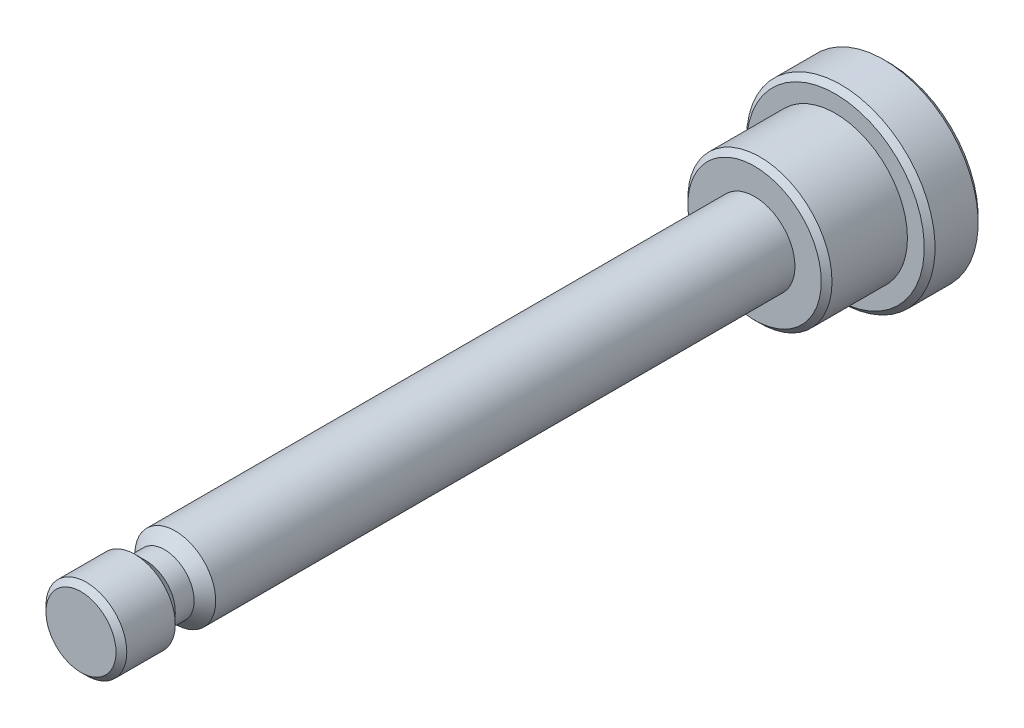
SolidWorks part; units mm, degrees
ref_plane "Front" through (0, 0, 0) normal (0, 0, 1) x (1, 0, 0)
ref_plane "Top" through (0, 0, 0) normal (0, 1, 0) x (1, 0, 0)
ref_plane "Right" through (0, 0, 0) normal (1, 0, 0) x (0, 0, -1)
sketch "Sketch1" plane through (0, 0, 0) normal (0, 0, 1) x (1, 0, 0)
  circle A0 centre (0, 0) radius 2.675
  dimension "D1" = 5.35
extrude "Countersink" add sketch "Sketch1" against normal blind 3
sketch "Sketch2" plane through (0, 0, 0) normal (0, 0, 1) x (1, 0, 0)
  circle A0 centre (0, 0) radius 1.5
  dimension "D1" = 3
extrude "Shaft" add sketch "Sketch2" along normal blind 25
sketch "Sketch3" plane through (0, 0, -3) normal (0, 0, -1) x (-1, 0, 0)
  circle A3 centre (0, 0) radius 3.5
  dimension "D1" = 7
extrude "Head" add sketch "Sketch3" along normal blind 2
sketch "Sketch4" plane through (0, 0, 0) normal (1, 0, 0) x (0, 0, -1)
  line L0 (0, 0) -> (-22.25, 0) construction
  line L1 (-22.25, 0) -> (-22.25, 4.3666) construction
  line L2 (-23, 1.5) -> (-21.5, 1.5)
  line L3 (0, 1.5) -> (-25, 1.5) construction
  line L6 (-21.5, 1.5) -> (-21.9, 1.1)
  line L7 (-21.9, 1.1) -> (-22.6, 1.1)
  line L8 (-22.6, 1.1) -> (-23, 1.5)
  dimension "D1" = 22.25
  dimension "D2" = 1.5
  dimension "D3" = 45
  dimension "D4" = 0.4
revolve "e-Clip Notch" cut sketch "Sketch4" angle 360 about L0
chamfer "Deburs" distance 0.2 angle 45 4 edges at (1.5, 0, 25) (-3.5, 0, -3) (-3.5, 0, -5) (2.675, 0, 0)
equation "\"D1@Sketch1\"=\"Hardware Head Countersink Diameter@Box Assy.Assembly\"-.25mm"
equation "\"D1@Shaft\"=\"Hardware Length@Box Assy.Assembly\"+5mm"
equation "\"D1@Sketch4\"=\"Hardware Length@Box Assy.Assembly\" + 2.25mm"
equation "\"D1@Sketch2\"=\"Hardware Clearance Hole Diameter@Box Assy.Assembly\"-.15"
